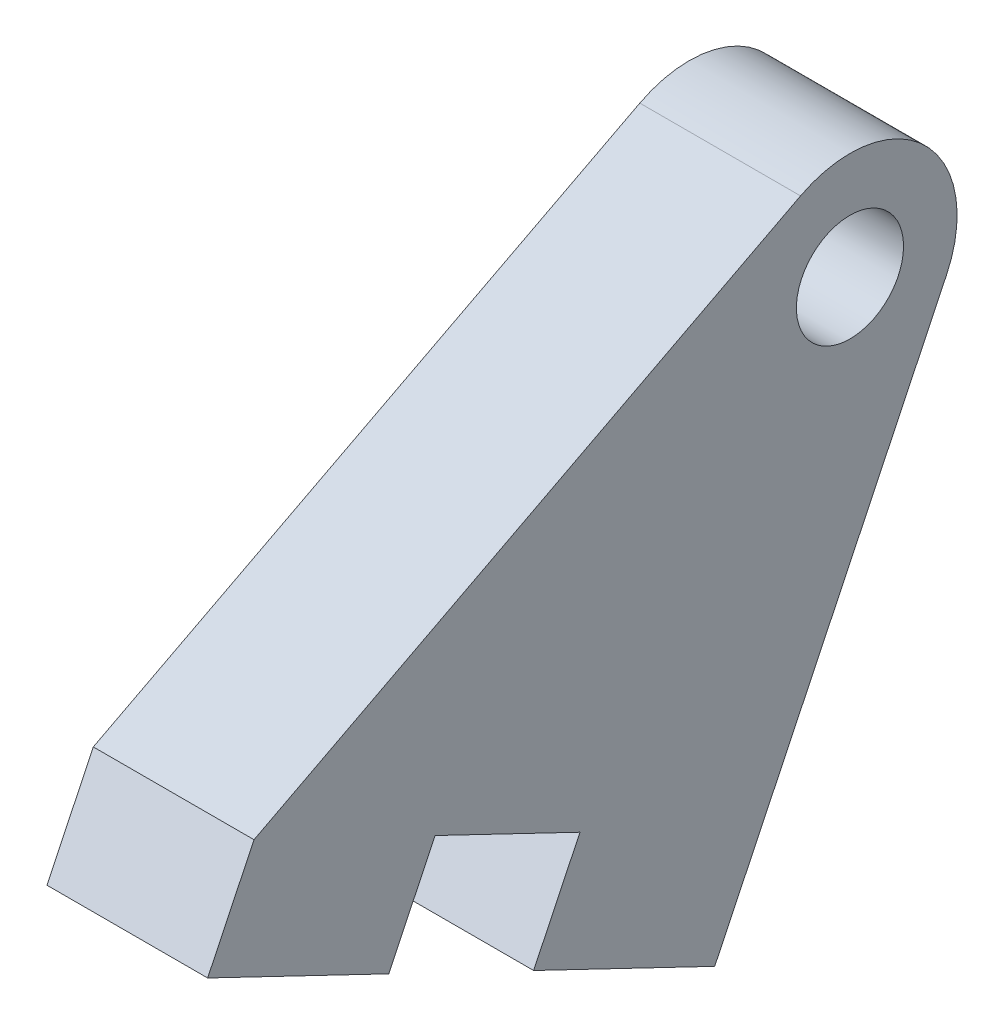
SolidWorks part; units mm, degrees
material "ABS PC"
ref_plane "Front" through (0, 0, 0) normal (0, 0, 1) x (1, 0, 0)
ref_plane "Top" through (0, 0, 0) normal (0, 1, 0) x (1, 0, 0)
ref_plane "Right" through (0, 0, 0) normal (1, 0, 0) x (0, 0, -1)
sketch "Sketch1" plane through (0, 0, 0) normal (1, 0, 0) x (0, 0, -1)
  line L0 (-96.6269, 8.8786) -> (-101.7279, 6.225)
  line L1 (-101.7279, 6.225) -> (-102.1607, 5.3235)
  line L2 (-102.1607, 5.3235) -> (-97.4279, 3.0513)
  line L3 (-97.4279, 3.0513) -> (-95.2639, 7.5587)
  line L4 (-99.7943, 4.1874) -> (-97.8467, 8.2441) construction
  line L5 (-100.4704, 4.512) -> (-100.0376, 5.4135)
  line L6 (-100.0376, 5.4135) -> (-98.6854, 4.7643)
  line L7 (-98.6854, 4.7643) -> (-99.1182, 3.8628)
  circle A0 centre (-96.1653, 7.9915) radius 0.5
  circle A1 centre (-96.1653, 7.9915) radius 1
  point P12 (-99.3615, 5.0889)
  dimension "D2" = 1
  dimension "D3" = 0.5
  dimension "D1" = 1
  dimension "D4" = 5.25
  dimension "D5" = 5
  dimension "D6" = 1
  dimension "D7" = 1.5
extrude "Boss-Extrude1" add sketch "Sketch1" along normal blind 1.5 contours A1 L0 L1 L2 L3 | A1 A0 | L6 L4 L0 L1 L2 L5 region at (0, 5.7077, 97.5792) region at (0, 8.8222, 95.6611) region at (0, 6.1857, 100.0667)
